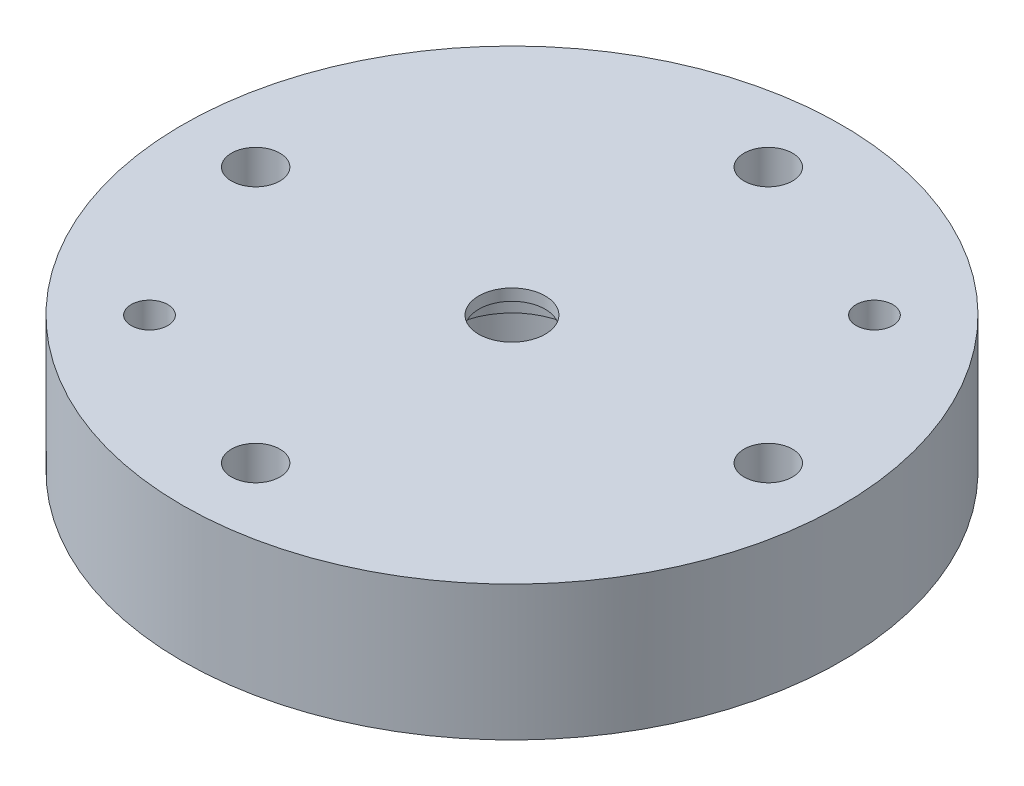
SolidWorks part; units mm, degrees
ref_plane "Front Plane" through (0, 0, 0) normal (0, 0, 1) x (1, 0, 0)
ref_plane "Top Plane" through (0, 0, 0) normal (0, 1, 0) x (1, 0, 0)
ref_plane "Right Plane" through (0, 0, 0) normal (1, 0, 0) x (0, 0, -1)
sketch "Sketch1" plane through (0, 0, 0) normal (0, 1, 0) x (1, 0, 0)
  circle A0 centre (0, 0) radius 57.15
  dimension "D1" = 114.3
extrude "seal seat hieght" add sketch "Sketch1" against normal blind 5.5372 contours A0
ref_plane "top end of seal" through (0, 0, 0) normal (0, 1, 0) x (1, 0, 0)
sketch "Sketch2" plane through (0, -5.5372, 0) normal (0, -1, 0) x (1, 0, 0)
  circle A1 centre (0, 0) radius 57.15
  circle A2 centre (0, 0) radius 57.15
  dimension "D1" = 0
extrude "seal diaphram hieght" add sketch "Sketch2" along normal blind 15.875
ref_plane "bottom end of seal" through (0, -21.4122, 0) normal (0, -1, 0) x (-1, 0, 0)
sketch "Sketch3" plane through (0, 0, 0) normal (0, 1, 0) x (1, 0, 0)
  circle A1 centre (0, 0) radius 57.15
  circle A2 centre (0, 0) radius 57.15
  dimension "D1" = 0
extrude "seal shoulder hieght" add sketch "Sketch3" along normal blind 2
sketch "Sketch4" plane through (0, -21.4122, 0) normal (0, -1, 0) x (1, 0, 0)
  circle A1 centre (0, 0) radius 57.15
  circle A2 centre (0, 0) radius 57.15
  dimension "D1" = 0
sketch "Sketch5" plane through (0, 0, 0) normal (0, 1, 0) x (1, 0, 0)
  circle A0 centre (0, 0) radius 11.1125
  dimension "D1" = 22.225
extrude "seal seat fit" cut sketch "Sketch5" against normal blind 5.5372
sketch "Sketch6" plane through (0, -21.4122, 0) normal (0, -1, 0) x (-1, 0, 0)
  circle A0 centre (0, 0) radius 12.7
  dimension "D1" = 25.4
sketch "Sketch7" plane through (0, 0, 0) normal (0, 1, 0) x (1, 0, 0)
  circle A0 centre (0, 0) radius 4.7625 construction
  circle A1 centre (0, 0) radius 5.7625
  dimension "D1" = 9.525
  dimension "D2" = 1
extrude "shaft clearance" cut sketch "Sketch7" along normal up to surface (2 mm away) up to face at (0, 2, 57.15)
sketch "bolt circle" plane through (0, 2, 0) normal (0, 1, 0) x (1, 0, 0)
  circle A0 centre (0, 0) radius 44.45 construction
  point P3 (-44.45, 0)
  point P4 (0, 44.45)
  point P5 (44.45, 0)
  point P6 (0, -44.45)
  dimension "D1" = 88.9
hole_wizard "M8 Clearance Hole1" positions "Sketch11" profile "Sketch12" hole size "M8" standard "ANSI Metric" end condition through all
sketch "Sketch11" plane through (0, 2, 0) normal (0, 1, 0) x (1, 0, 0)
  point P0 (-44.45, 0)
  point P3 (0, 44.45)
  point P6 (44.45, 0)
  point P9 (0, -44.45)
sketch "Sketch12" plane through (-44.45, 2, 0) normal (1, 0, 0) x (0, 0, 1)
  line L0 (0, 0) -> (0, 23.4122)
  line L1 (0, 23.4122) -> (4.2, 23.4122)
  line L2 (4.2, 23.4122) -> (4.2, 0)
  line L5 (4.2, 0) -> (0, 0)
  line L11 (0, -6.35) -> (0, 107.95) construction
  dimension "Thru Hole Dia." = 8.4
  dimension "Thru Hole Depth" = 23.4122
sketch "dowel hole positioning " plane through (0, 2, 0) normal (0, 1, 0) x (1, 0, 0)
  line L0 (0, 0) -> (53.8672, 0) construction
  line L1 (-31.4309, -31.4309) -> (31.4309, 31.4309) construction
  circle A0 centre (0, 0) radius 44.45 construction
  circle A1 centre (0, 0) radius 44.45 construction
  point P8 (0, 0)
  point P9 (31.4309, 31.4309)
  point P10 (-31.4309, -31.4309)
  dimension "D1" = 45
hole_wizard "1/4 (0.25) Press Dowel Hole1" positions "Sketch14" profile "Sketch15" hole size "1/4" standard "ANSI Inch" end condition through all
sketch "Sketch14" plane through (0, 2, 0) normal (0, 1, 0) x (1, 0, 0)
  point P0 (31.4309, 31.4309)
  point P3 (-31.4309, -31.4309)
sketch "Sketch15" plane through (31.4309, 2, -31.4309) normal (1, 0, 0) x (0, 0, 1)
  line L0 (0, 0) -> (0, 23.4122)
  line L1 (0, 23.4122) -> (3.175, 23.4122)
  line L2 (3.175, 23.4122) -> (3.175, 0)
  line L5 (3.175, 0) -> (0, 0)
  line L11 (0, -6.35) -> (0, 107.95) construction
  dimension "Thru Hole Dia." = 6.35
  dimension "Thru Hole Depth" = 23.4122
extrude "Cut-Extrude1" cut sketch "Sketch6" against normal up to surface (15.875 mm away) up to face at (0, -5.5372, 11.1125)
sketch "Sketch16" plane through (0, 2, 0) normal (0, 1, 0) x (1, 0, 0)
  line L1 (-60, 60) -> (60, 60)
  line L2 (-60, 60) -> (-60, -60)
  line L3 (-60, -60) -> (60, -60)
  line L4 (60, 60) -> (60, -60)
  line L5 (-60, 60) -> (60, -60) construction
  line L6 (-60, -60) -> (60, 60) construction
  point P0 (0, 0)
  dimension "D1" = 120
  dimension "D2" = 120
equation "\"seal seat height\"=5.5372"
equation "\"D1@seal seat hieght\" = \"seal seat height\""
equation "\"seal diaphram height\"=15.875"
equation "\"D1@seal diaphram hieght\" = \"seal diaphram height\""
equation "\"seal shoulder height\"=2"
equation "\"D1@seal shoulder hieght\" = \"seal shoulder height\""
equation "\"seal seat OD\"= .875in"
equation "\"D1@Sketch5\"=\"seal seat OD\""
equation "\"D1@seal seat fit\" = \"seal seat height\""
equation "\"seal diaphram clearance\"=25.4"
equation "\"D1@Sketch6\"=\"seal diaphram clearance\""
equation "\"seal ID\"=9.525"
equation "\"D1@Sketch7\"=\"seal ID\""
equation "\"bolt circle dia\"=88.9"
equation "\"D1@bolt circle\" = \"bolt circle dia\""
